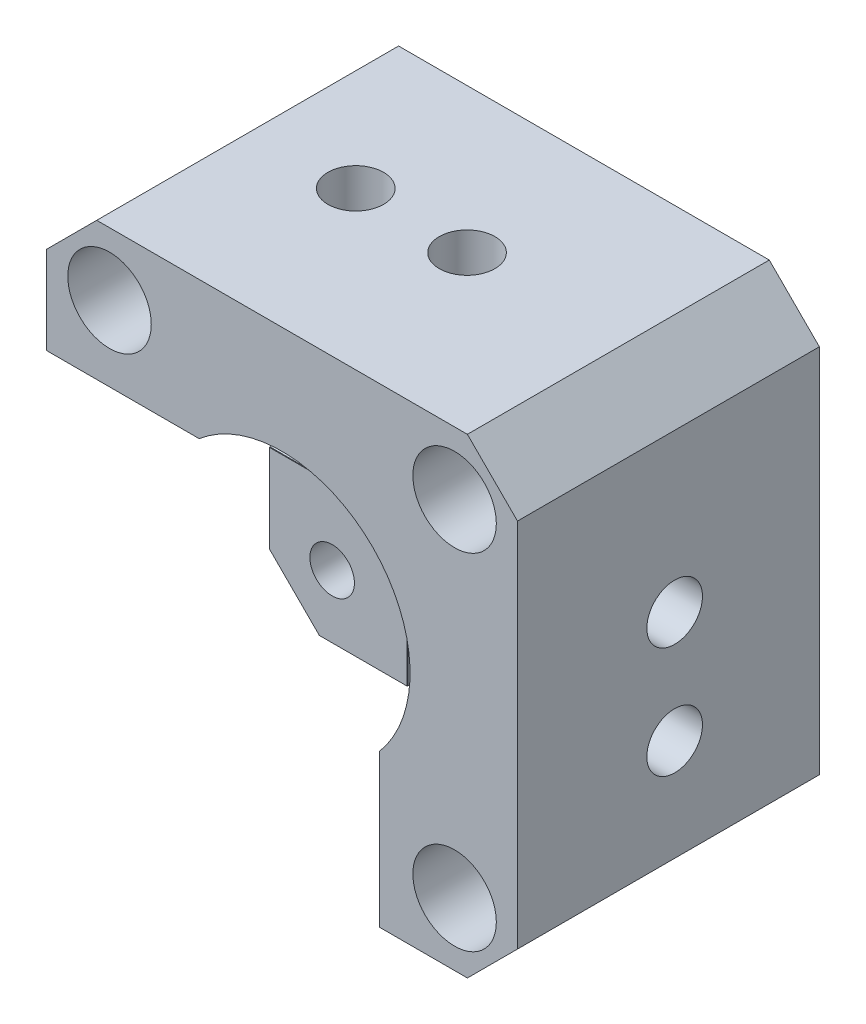
SolidWorks part; units mm, degrees
ref_plane "Front Plane" through (0, 0, 0) normal (0, 0, 1) x (1, 0, 0)
ref_plane "Top Plane" through (0, 0, 0) normal (0, 1, 0) x (1, 0, 0)
ref_plane "Right Plane" through (0, 0, 0) normal (1, 0, 0) x (0, 0, -1)
sketch "Sketch1" plane through (0, 0, 0) normal (0, 0, 1) x (1, 0, 0)
  line L0 (-15.5, 15.5) -> (-15.5, -15.5) construction
  line L1 (-15.5, -15.5) -> (15.5, -15.5) construction
  line L2 (15.5, -15.5) -> (15.5, 15.5) construction
  line L3 (15.5, 15.5) -> (-15.5, 15.5) construction
  line L4 (-15.5, 15.5) -> (15.5, -15.5) construction
  line L8 (-14.15, -21.15) -> (14.15, -21.15)
  line L9 (14.15, -21.15) -> (21.15, -14.15)
  line L10 (21.15, -14.15) -> (21.15, 14.15)
  line L11 (21.15, 14.15) -> (14.15, 21.15)
  line L12 (14.15, 21.15) -> (-14.15, 21.15)
  line L13 (-14.15, 21.15) -> (-21.15, 14.15)
  line L14 (-21.15, 14.15) -> (-21.15, -14.15)
  line L15 (-21.15, -14.15) -> (-14.15, -21.15)
  line L16 (-21.15, -21.15) -> (21.15, -21.15)
  line L18 (21.15, -21.15) -> (21.15, 21.15)
  line L20 (21.15, 21.15) -> (-21.15, 21.15)
  line L22 (-21.15, 21.15) -> (-21.15, -21.15)
  circle A1 centre (0, 0) radius 11.5
  circle A6 centre (-15.5, 15.5) radius 2
  circle A7 centre (15.5, 15.5) radius 2
  circle A8 centre (15.5, -15.5) radius 2
  circle A9 centre (-15.5, -15.5) radius 2
  point P1 (0, 0)
  dimension "D2" = 23
  dimension "D3" = 4
  dimension "D4" = 31
  dimension "D1" = 0
extrude "Boss-Extrude1" add sketch "Sketch1" along normal up to surface (27.12 mm away)
sketch "Sketch2" plane through (0, -21.15, 0) normal (0, -1, 0) x (1, 0, 0)
  line L0 (-8.761, 27.12) -> (-8.761, 3.05)
  line L1 (21.15, 27.12) -> (-21.15, 27.12) construction
  line L2 (-8.761, 3.05) -> (8.7623, 3.05)
  line L3 (8.7623, 3.05) -> (8.7623, 27.12)
  line L4 (8.7623, 27.12) -> (-8.761, 27.12)
  line L11 (-4.8339, 11.4) -> (-6.761, 11.4)
  line L12 (-6.761, 11.4) -> (-6.761, 5.05)
  line L13 (-6.761, 5.05) -> (-4.8339, 5.05)
  line L14 (-4.8339, 5.05) -> (-4.8339, 11.4)
  line L15 (-4.8339, 11.4) -> (-6.761, 11.4) construction
  line L16 (-6.761, 11.4) -> (-6.761, 5.05) construction
  line L17 (-6.761, 5.05) -> (-4.8339, 5.05) construction
  line L18 (-4.8339, 5.05) -> (-4.8339, 11.4) construction
  line L19 (13.9216, 11.4) -> (6.7623, 11.4)
  line L20 (13.9216, 5.05) -> (13.9216, 11.4)
  line L21 (6.7623, 5.05) -> (13.9216, 5.05)
  line L22 (6.7623, 11.4) -> (6.7623, 5.05)
  line L26 (6.7623, 11.4) -> (6.7623, 5.05) construction
  dimension "D5" = 2
  dimension "D1" = 0
  dimension "D3" = 2
  dimension "D4" = 2
  dimension "D2" = 0
extrude "Cut-Extrude1" cut sketch "Sketch2" against normal up to next contours L3 L4 L0 L2
sketch "Sketch3" plane through (0, 0, 27.12) normal (0, 0, 1) x (1, 0, 0)
  circle A0 centre (15.5, 15.5) radius 3.75
  circle A1 centre (15.5, -15.5) radius 3.75
  circle A2 centre (-15.5, 15.5) radius 3.75
  circle A3 centre (-15.5, -15.5) radius 12.2465
  dimension "D1" = 7.5
extrude "Cut-Extrude2" cut sketch "Sketch3" against normal blind 20
sketch "Sketch4" plane through (0, 21.15, 0) normal (0, 1, 0) x (1, 0, 0)
  line L0 (0, 0) -> (0, -35.7016) construction
  line L2 (21.15, 0) -> (-21.15, 0) construction
  line L3 (-7.5, -13) -> (2.5, -13) construction
  circle A0 centre (-7.5, -13) radius 2.5
  circle A1 centre (2.5, -13) radius 2.5
  dimension "D1" = 5
  dimension "D2" = 7.5
  dimension "D3" = 13
  dimension "D4" = 10
extrude "Cut-Extrude3" cut sketch "Sketch4" against normal through all
ref_plane "Plane1" through (0, 0, 0) normal (-0.7071, 0.7071, 0) x (0, 0, 1)
sketch "Sketch6" plane through (0, 21.15, 0) normal (0, 1, 0) x (1, 0, 0)
  line L1 (-7.5, -17.65) -> (-3.473, -15.325)
  line L2 (-3.473, -15.325) -> (-3.473, -10.675)
  line L3 (-3.473, -10.675) -> (-7.5, -8.35)
  line L4 (-7.5, -8.35) -> (-11.527, -10.675)
  line L5 (-11.527, -10.675) -> (-11.527, -15.325)
  line L6 (-11.527, -15.325) -> (-7.5, -17.65)
  line L7 (2.5, -17.65) -> (6.527, -15.325)
  line L8 (6.527, -15.325) -> (6.527, -10.675)
  line L9 (6.527, -10.675) -> (2.5, -8.35)
  line L10 (2.5, -8.35) -> (-1.527, -10.675)
  line L11 (-1.527, -10.675) -> (-1.527, -15.325)
  line L12 (-1.527, -15.325) -> (2.5, -17.65)
  circle A0 centre (-7.5, -13) radius 4.027 construction
  circle A1 centre (2.5, -13) radius 4.027 construction
  circle A2 centre (-7.5, -13) radius 2.5 construction
  circle A3 centre (-7.5, -13) radius 2.5 construction
  dimension "D1" = 9.3
extrude "Cut-Extrude4" cut sketch "Sketch6" against normal through all from offset 4 offset against normal yes
mirror "Mirror1" about plane through (0, 0, 0) normal (-0.7071, 0.7071, 0) of "Cut-Extrude4", "Cut-Extrude1", "Cut-Extrude3"
chamfer "Chamfer1" distance 4.5 angle 45 4 edges at (-21.15, -21.15, 3.56) (21.15, 21.15, 13.56) (21.15, -21.15, 13.56) (-21.15, 21.15, 13.56)
chamfer "Chamfer2" distance 4 angle 45 4 edges at (8.7623, -14.299, 3.05) (-8.761, -14.9555, 3.05) (-14.9555, -8.761, 3.05) (-14.299, 8.7623, 3.05)
